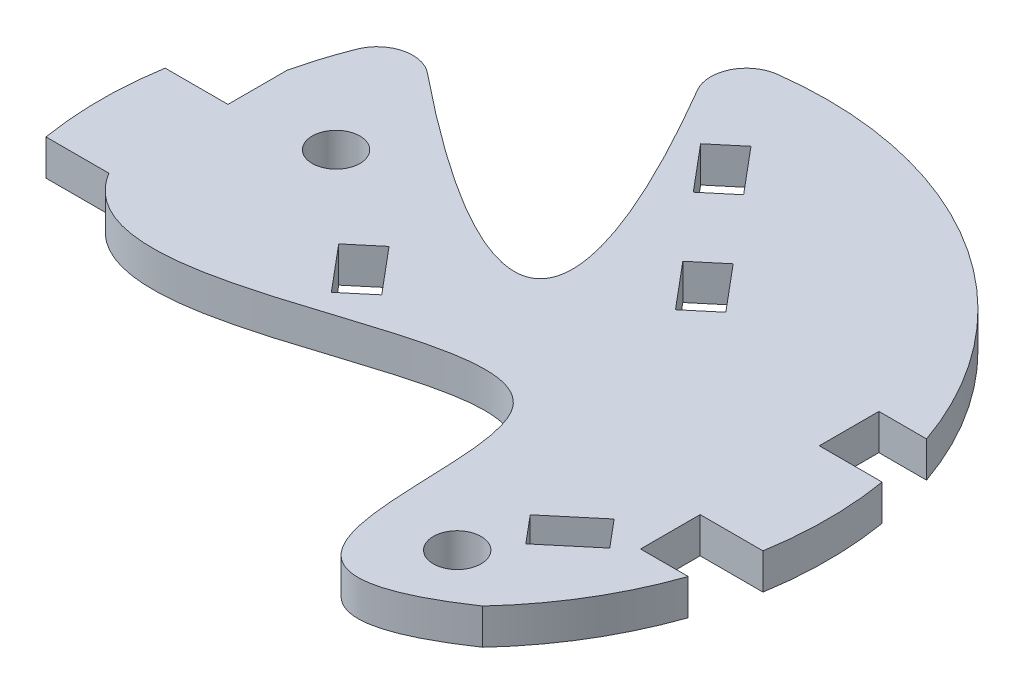
SolidWorks part; units mm, degrees
ref_plane "Alzado" through (0, 0, 0) normal (0, 0, 1) x (1, 0, 0)
ref_plane "Planta" through (0, 0, 0) normal (0, 1, 0) x (1, 0, 0)
ref_plane "Vista lateral" through (0, 0, 0) normal (1, 0, 0) x (0, 0, -1)
sketch "Croquis1" plane through (0, 0, 0) normal (0, 1, 0) x (1, 0, 0)
  circle A0 centre (0, 0) radius 30.5
extrude "Saliente-Extruir1" add sketch "Croquis1" along normal blind 3
sketch "Croquis5" plane through (0, 3, 0) normal (0, 1, 0) x (1, 0, 0)
  line L0 (0, 0) -> (0, 10)
  line L1 (28.8141, -5) -> (30.0874, -5)
  line L2 (28.8141, 5) -> (30.0874, 5)
  line L3 (-24.8141, 10) -> (-28.8141, 10)
  line L4 (24.8141, -5) -> (24.8141, -10)
  line L5 (-24.8141, -10) -> (-28.8141, -10)
  line L6 (24.8141, -5) -> (28.8141, -5)
  line L7 (24.8141, 5) -> (24.8141, 10)
  line L8 (-24.8141, 5) -> (-28.8141, 5)
  line L9 (-24.8141, 5) -> (-24.8141, 10)
  line L10 (-24.8141, -5) -> (-28.8141, -5)
  line L11 (-24.8141, -5) -> (-24.8141, -10)
  line L12 (24.8141, 5) -> (28.8141, 5)
  line L13 (24.8141, -10) -> (28.8141, -10)
  line L14 (24.8141, 10) -> (28.8141, 10)
  line L15 (-28.8141, 5) -> (-30.0874, 5)
  line L16 (-28.8141, -5) -> (-30.0874, -5)
  circle A1 centre (0, 0) radius 30.5 construction
  arc A2 (-28.8141, 10) -> (-30.0874, 5) centre (0, 0) ccw
  arc A3 (28.8141, 10) -> (28.8141, -10) centre (0, 0) cw
  arc A4 (-30.0874, -5) -> (-28.8141, -10) centre (0, 0) ccw
  arc A5 (30.0874, -5) -> (28.8141, -10) centre (0, 0) cw
  arc A6 (28.8141, 10) -> (30.0874, 5) centre (0, 0) cw
  circle M2 centre (0, 0) radius 30.5
extrude "Cortar-Extruir3" cut sketch "Croquis5" against normal blind 4 contours L11 L10 L8 L9 L3 L5 M2 | L15 L8 L9 L3 M2 | L14 L7 L12 L2 M2 | L4 L13 L1 L6 M2 region at (27.1844, 3, 7.3876) region at (27.1844, 3, -7.3876) region at (-27.1844, 3, 7.3876) region at (-27.1844, 3, -7.3876)
sketch "Croquis9" plane through (0, 3, 0) normal (0, 1, 0) x (1, 0, 0)
  line L0 (7.2803, 10.7703) -> (22.8679, -7.8063)
  line L1 (-8.3073, 29.3469) -> (7.2803, 10.7703)
  line L2 (7.9714, 14.6138) -> (11.1854, 10.7835)
  line L3 (-24.8141, -5) -> (-24.8141, -10)
  line L4 (-24.8141, -10) -> (-28.8141, -10)
  line L5 (11.1854, 10.7835) -> (8.8872, 8.8552)
  line L6 (-7.7325, 1.4366) -> (-10.0306, -0.4918)
  line L7 (7.9714, 14.6138) -> (5.6733, 12.6854)
  line L8 (-10.0306, -0.4918) -> (-6.8167, -4.322)
  line L9 (-6.8167, -4.322) -> (-4.5186, -2.3936)
  line L10 (21.5273, -8.9312) -> (23.4556, -11.2293)
  line L11 (-2.1205, 21.9737) -> (1.0934, 18.1435)
  line L12 (0.1776, 23.902) -> (3.3916, 20.0718)
  line L13 (-24.8141, 10) -> (-28.8141, 10)
  line L14 (3.3916, 20.0718) -> (1.0934, 18.1435)
  line L15 (0.1776, 23.902) -> (-2.1205, 21.9737)
  line L20 (-7.7325, 1.4366) -> (-4.5186, -2.3936)
  line L21 (17.6971, -12.1451) -> (19.6254, -14.4432)
  line L23 (19.6254, -14.4432) -> (23.4556, -11.2293)
  line L27 (17.6971, -12.1451) -> (21.5273, -8.9312)
  arc A1 (28.8141, 10) -> (-28.8141, 10) centre (0, 0) ccw construction
  circle A4 centre (-16.9835, 6.2386) radius 2
  arc A5 (-28.8141, -10) -> (28.8141, -10) centre (0, 0) ccw construction
  arc A6 (-23.4189, 14.4323) -> (-18.7453, 15.6646) centre (-20.6289, 13.3296) cw
  arc A7 (-28.8141, -10) -> (22.3289, -20.7766) centre (0, 0) ccw
  arc A8 (-28.8141, 10) -> (-8.3073, 29.3469) centre (0, 0) cw
  circle A9 centre (17.204, -17.7804) radius 2
  spline S0 degree 3 poles (22.3289, -20.7766) (5.9738, -31.8512) (22.1768, 15.8352) (-18.2069, -15.8076) (-24.8141, -5) knots 0 0 0 0 0.44579 1 1 1 1
  spline S1 degree 3 poles (-24.8141, -5) (-26.3603, 1.5896) (-25.8363, 8.3159) (-23.4189, 14.4323) knots 0 0 0 0 0.831813 0.831813 0.831813 0.831813
  spline S2 degree 3 poles (-18.7453, 15.6646) (3.867, -2.5765) (8.0942, 2.4964) (-8.3073, 29.3469) knots 0.040528 0.040528 0.040528 0.040528 1 1 1 1
  arc M16 (28.8141, 10) -> (-28.8141, 10) centre (0, 0) ccw
  line M17 (-28.8141, 10) -> (-24.8141, 10)
  line M22 (-24.8141, -5) -> (-24.8141, -10)
  line M42 (-24.8141, -10) -> (-28.8141, -10)
  arc M43 (-28.8141, -10) -> (28.8141, -10) centre (0, 0) ccw
  dimension "D1" = 3
extrude "Cortar-Extruir6" cut sketch "Croquis9" against normal blind 10 contours L2 L7 | S0 M43 M22 M42 | A6 S2 S1 M16 M17 | L20 | A4 | A9 | L27 L21 L23 | L12 L15 L1 L14 region at (8.4293, 3, -11.7345) region at (-4.7635, 3, 17.3355) region at (-10.9842, 3, -16.8529) region at (0.6355, 3, -21.0227) region at (-7.2746, 3, 1.4427) region at (20.5763, 3, 11.6872) region at (-16.9835, 3, -6.2386) region at (17.204, 3, 17.7804)
fillet "Redondeo1" radius 3 1 edges at (-8.3073, 1.5, -29.3469)
